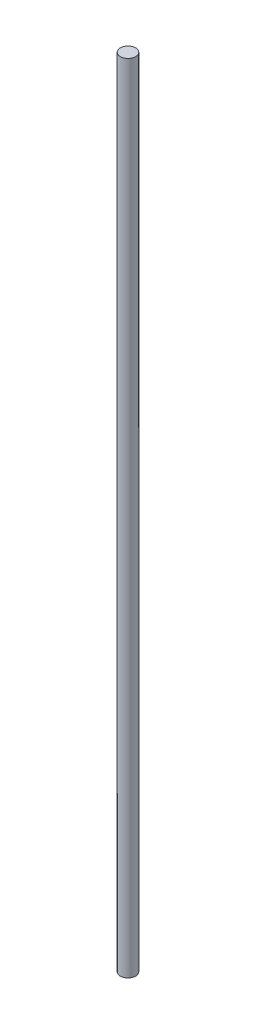
SolidWorks part; units mm, degrees
ref_plane "Ebene vorne" through (0, 0, 0) normal (0, 0, 1) x (1, 0, 0)
ref_plane "Ebene oben" through (0, 0, 0) normal (0, 1, 0) x (1, 0, 0)
ref_plane "Ebene rechts" through (0, 0, 0) normal (1, 0, 0) x (0, 0, -1)
sketch "Position" plane through (0, 0, 0) normal (0, 1, 0) x (1, 0, 0)
  circle A0 centre (14, 0) radius 1.5
  circle A1 centre (0, 0) radius 4.5
sketch "Length" plane through (0, 0, 0) normal (0, 0, 1) x (1, 0, 0)
  line L0 (0, 200) -> (0, 550)
  line L4 (14, 237) -> (14, 550)
sketch "Skizze3" plane through (0, 0, 0) normal (0, 1, 0) x (1, 0, 0)
  circle A0 centre (14, 0) radius 3
extrude "Aufsatz-Linear austragen1" add sketch "Skizze3" along normal up to vertex (550 mm away) from vertex up to point (14, 550, 0) starting at point (14, 237, 0)
sketch "Skizze4" plane through (0, 0, 0) normal (0, 1, 0) x (1, 0, 0)
  circle A0 centre (14, 0) radius 1.25
extrude "Schnitt-Linear austragen1" cut sketch "Skizze4" along normal blind 20 from vertex starting at point (14, 237, 0)
